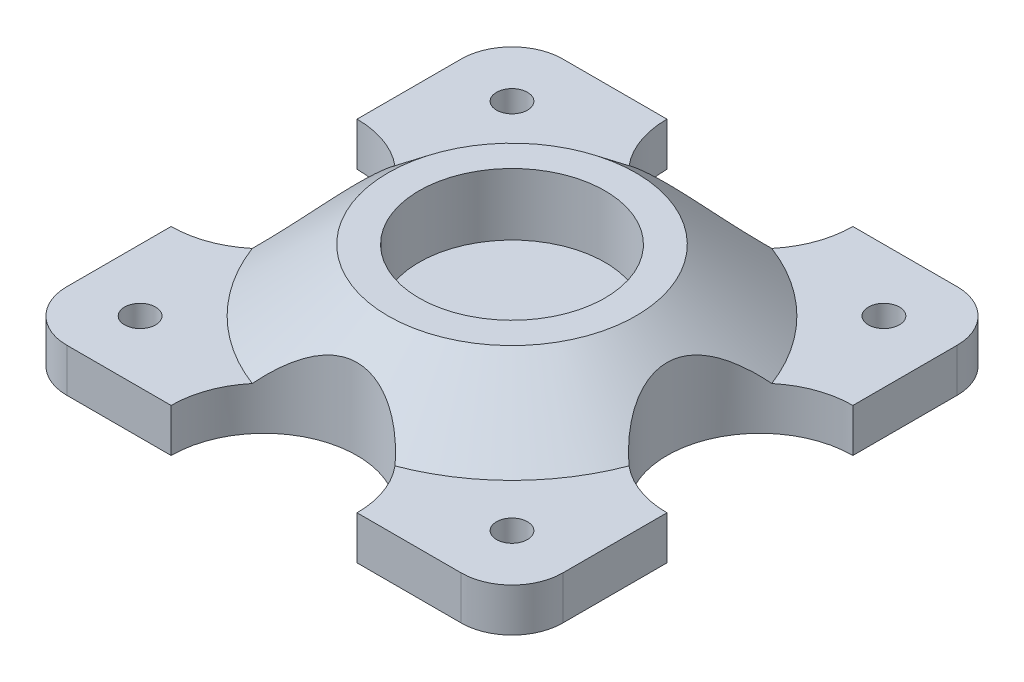
SolidWorks part; units mm, degrees
ref_plane "Front Plane" through (0, 0, 0) normal (0, 0, 1) x (1, 0, 0)
ref_plane "Top Plane" through (0, 0, 0) normal (0, 1, 0) x (1, 0, 0)
ref_plane "Right Plane" through (0, 0, 0) normal (1, 0, 0) x (0, 0, -1)
sketch "Sketch2" plane through (0, 0, 0) normal (0, 1, 0) x (1, 0, 0)
  line L1 (-40.4, -50.8) -> (40.4, -50.8)
  line L2 (-50.8, -40.4) -> (-50.8, 40.4)
  line L3 (-40.4, 50.8) -> (40.4, 50.8)
  line L4 (50.8, -40.4) -> (50.8, 40.4)
  line L5 (-50.8, -50.8) -> (50.8, 50.8) construction
  line L6 (-50.8, 50.8) -> (50.8, -50.8) construction
  circle A0 centre (50.8, 0) radius 19.05
  circle A1 centre (0, 50.8) radius 19.05
  circle A2 centre (-50.8, 0) radius 19.05
  circle A3 centre (0, -50.8) radius 19.05
  circle A4 centre (38.1, 38.1) radius 3.175
  circle A5 centre (38.1, -38.1) radius 3.175
  circle A6 centre (-38.1, -38.1) radius 3.175
  circle A7 centre (-38.1, 38.1) radius 3.175
  arc A8 (40.4, -50.8) -> (50.8, -40.4) centre (40.4, -40.4) ccw
  arc A9 (-40.4, -50.8) -> (-50.8, -40.4) centre (-40.4, -40.4) cw
  arc A10 (-50.8, 40.4) -> (-40.4, 50.8) centre (-40.4, 40.4) cw
  arc A11 (40.4, 50.8) -> (50.8, 40.4) centre (40.4, 40.4) cw
  point P0 (0, 0)
  dimension "D3" = 38.1
  dimension "D4" = 6.35
  dimension "D7" = 10.4
  dimension "D1" = 101.6
  dimension "D2" = 101.6
  dimension "D5" = 12.7
  dimension "D6" = 12.7
extrude "Boss-Extrude2" add sketch "Sketch2" along normal blind 8.89 contours L3 A1 | L2 A2 | L1 A3 | L4 A0 | A11 L3 A1 A10 L2 A2 A9 L1 A3 A8 L4 A0 A7 A6 A5 A4 region at (0, 0, 0) region at (0, 0, 42.7149) region at (42.7149, 0, 0) region at (-42.7149, 0, 0) region at (0, 0, -42.7149)
sketch "Sketch4" plane through (0, 8.89, 0) normal (0, 1, 0) x (1, 0, 0)
  circle A0 centre (0, 0) radius 41.275
  circle A1 centre (0, 0) radius 25.4
  circle A2 centre (0, 0) radius 19.05
  dimension "D1" = 82.55
  dimension "D2" = 38.1
  dimension "D3" = 50.8
extrude "Boss-Extrude3" add sketch "Sketch4" along normal blind 12.7 contours A1 A2 region at (-24.6816, 8.89, 0)
loft "Loft1" add section edge at (0, 21.59, 25.4) section "Sketch4<3>" connector at (21.4702, 21.59, -13.5718) connector at (35.593, 8.89, -20.899)
sketch "Sketch4<3>" plane through (0, 8.89, 0) normal (0, 1, 0) x (1, 0, 0) same geometry as "Sketch4"
extrude "Cut-Extrude1" cut sketch "Sketch4<4>" along normal through all contours A2
sketch "Sketch4<4>" plane through (0, 8.89, 0) normal (0, 1, 0) x (1, 0, 0) same geometry as "Sketch4"
extrude "Cut-Extrude2" cut sketch "Sketch2<3>" along normal through all contours L2 A2 | L3 A1 | L4 A0 | L1 A3 region at (0, 0, 42.7149) region at (42.7149, 0, 0) region at (-42.7149, 0, 0) region at (0, 0, -42.7149)
sketch "Sketch2<3>" plane through (0, 0, 0) normal (0, 1, 0) x (1, 0, 0) same geometry as "Sketch2"
